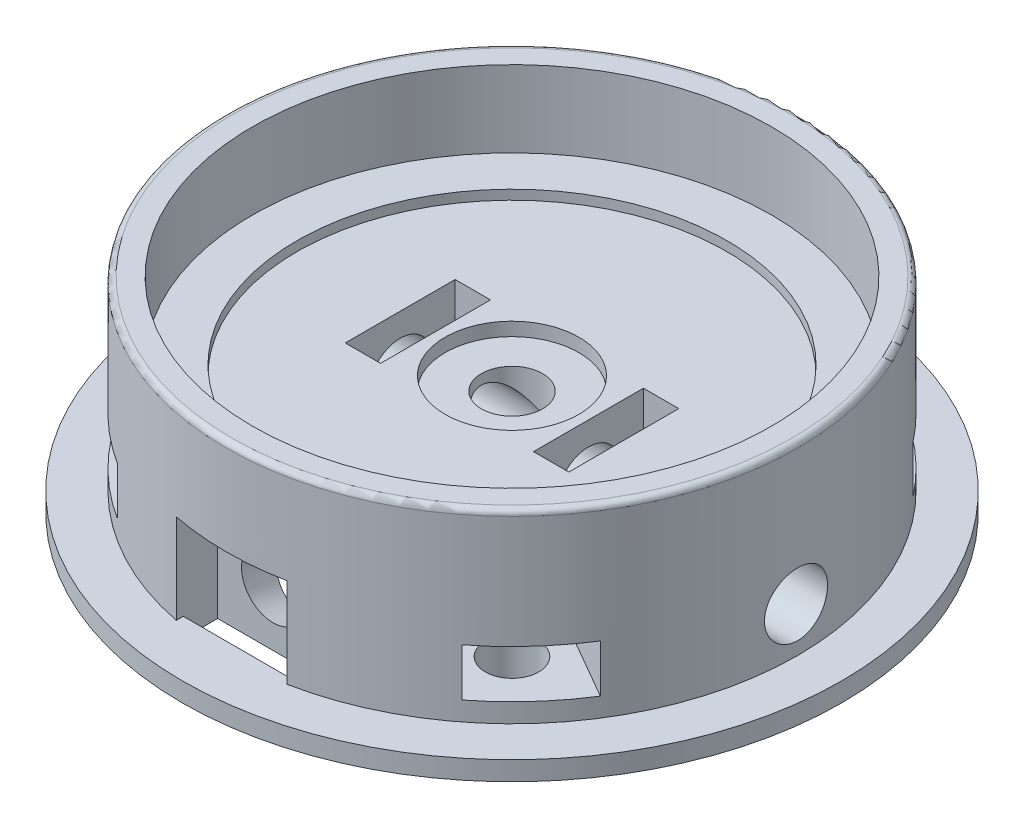
SolidWorks part; units mm, degrees
ref_plane "Front Plane" through (0, 0, 0) normal (0, 0, 1) x (1, 0, 0)
ref_plane "Top Plane" through (0, 0, 0) normal (0, 1, 0) x (1, 0, 0)
ref_plane "Right Plane" through (0, 0, 0) normal (1, 0, 0) x (0, 0, -1)
sketch "Sketch1" plane through (0, 0, 0) normal (0, 1, 0) x (1, 0, 0)
  circle A0 centre (0, 0) radius 14.95
  dimension "D1" = 29.9
extrude "Boss-Extrude1" add sketch "Sketch1" along normal blind 5.7
sketch "Sketch2" plane through (0, 5.7, 0) normal (0, 1, 0) x (1, 0, 0)
  circle A0 centre (0, 0) radius 11.25
  dimension "D1" = 22.5
extrude "Cut-Extrude1" cut sketch "Sketch2" against normal blind 0.5
sketch "Sketch3" plane through (0, 5.7, 0) normal (0, 1, 0) x (1, 0, 0)
  circle A0 centre (0, 0) radius 13.575
  circle A1 centre (0, 0) radius 14.95
  circle A2 centre (0, 0) radius 14.95 construction
  dimension "D1" = 27.15
extrude "Boss-Extrude2" add sketch "Sketch3" along normal blind 4
fillet "Fillet1" radius 0.3 1 edges at (0, 9.7, 14.95)
sketch "Sketch4" plane through (0, 5.2, 0) normal (0, 1, 0) x (1, 0, 0)
  circle A0 centre (0, 0) radius 1.6
  dimension "D1" = 3.2
extrude "Cut-Extrude2" cut sketch "Sketch4" against normal through all
ref_plane "Plane1" through (4, 0, 0) normal (1, 0, 0) x (0, 0, -1)
sketch "Sketch5" plane through (0, 0, 0) normal (1, 0, 0) x (0, 0, -1)
  line L1 (1.6, 5.2) -> (-1.6, 5.2) construction
  line L2 (-2.875, -0.55) -> (2.875, -0.55) construction
  line L3 (-2.875, -0.55) -> (-2.875, 5.2) construction
  line L4 (-2.875, 5.2) -> (2.875, 5.2) construction
  line L5 (2.875, -0.55) -> (2.875, 5.2) construction
  line L6 (-2.875, -0.55) -> (2.875, 5.2) construction
  line L7 (-2.875, 5.2) -> (2.875, -0.55) construction
  circle A0 centre (0, 2.325) radius 1.65
  dimension "D1" = 3.3
  dimension "D2" = 5.75
extrude "Cut-Extrude3" cut sketch "Sketch5" along normal through all
sketch "Sketch6" plane through (0, 0, 0) normal (0, -1, 0) x (1, 0, 0)
  circle A0 centre (0, 0) radius 1.6 construction
  circle A1 centre (0, 0) radius 1.6
  circle A2 centre (0, 0) radius 17.25
  dimension "D1" = 34.5
extrude "Boss-Extrude3" add sketch "Sketch6" along normal blind 1
sketch "Sketch7" plane through (4, 0, 0) normal (1, 0, 0) x (0, 0, -1)
  line L7 (-2.875, 5.2) -> (2.875, 5.2)
  line L8 (-2.875, 5.2) -> (-2.875, -0.55)
  line L9 (-2.875, -0.55) -> (2.875, -0.55)
  line L10 (2.875, 5.2) -> (2.875, -0.55)
  line L11 (-2.875, 5.2) -> (2.875, -0.55) construction
  line L12 (-2.875, -0.55) -> (2.875, 5.2) construction
  point P1 (0, 2.325)
  dimension "D2" = 5.75
extrude "Cut-Extrude4" cut sketch "Sketch7" along normal blind 1.85
ref_axis "Axis1" through (0, 9.4, 0) along (0, -1, 0)
pattern_circular "CirPattern1" count 2 over 360 about axis through (0, 9.4, 0) along (0, -1, 0) of "Cut-Extrude4", "Cut-Extrude3"
ref_plane "Plane2" through (0, 0, 0) normal (0, 0, 1) x (0, -1, 0)
ref_plane "Plane3" through (0, 0, 12.5) normal (0, 0, 1) x (0, -1, 0)
sketch "Sketch11" plane through (0, 0, 12.5) normal (0, 0, 1) x (0, -1, 0)
  line L0 (0, 23.2225) -> (0, -23.2225) construction
  point P4 (0, 0)
ref_plane "Plane4" through (0, 2.5421, 11.9597) normal (0, 0.2079, 0.9781) x (-1, 0, 0)
sketch "Sketch9" plane through (0, 0.4189, 12.411) normal (0, 0.2079, 0.9781) x (0, -0.9781, 0.2079)
  line L0 (-11.3652, 0) -> (-2.1706, 0) construction
  line L2 (1.4283, 2.9) -> (-4.3717, 2.9) construction
  line L3 (1.4283, 2.9) -> (1.4283, -2.9) construction
  line L4 (1.4283, -2.9) -> (-4.3717, -2.9) construction
  line L5 (-4.3717, 2.9) -> (-4.3717, -2.9) construction
  line L6 (1.4283, 2.9) -> (-4.3717, -2.9) construction
  line L7 (1.4283, -2.9) -> (-4.3717, 2.9) construction
  line L8 (0.4283, 23.2225) -> (0.4283, -23.2225) construction
  circle A0 centre (-1.4717, 0) radius 1.65
  dimension "D2" = 3.3
  dimension "D1" = 5.8
  dimension "D3" = 1
extrude "Cut-Extrude5" cut sketch "Sketch9" along normal through all and the other way blind 2
sketch "Sketch10" plane through (0, 0, 12.5) normal (0, 0, 1) x (0, -1, 0)
  line L1 (0.9781, 2.9) -> (-4.6951, 2.9) construction
  line L2 (-4.6951, 2.9) -> (-4.6951, -2.9) construction
  line L3 (0.9781, -2.9) -> (-4.6951, -2.9) construction
  line L5 (0.9781, 2.9) -> (-4.6951, 2.9)
  line L6 (-4.6951, 2.9) -> (-4.6951, -2.9)
  line L7 (0.9781, -2.9) -> (-4.6951, -2.9)
  line L8 (0.9781, 2.9) -> (2.9781, 2.9)
  line L9 (2.9781, 2.9) -> (2.9781, -2.9)
  line L10 (2.9781, -2.9) -> (0.9781, -2.9)
  dimension "D1" = 2
extrude "Cut-Extrude6" cut sketch "Sketch10" along normal blind 1.8
ref_plane "Plane5" through (0, 2.2302, 10.4924) normal (0, 0.2079, 0.9781) x (-1, 0, 0)
sketch "Sketch13" plane through (0, 2.2302, 10.4924) normal (0, 0.2079, 0.9781) x (-1, 0, 0)
  line L0 (-2.4902, -0.2075) -> (-3.8756, 3.5989)
  line L1 (-3.8756, 3.5989) -> (3.8756, 3.5989)
  line L2 (3.8756, 3.5989) -> (2.4902, -0.2075)
  line L3 (0, 0.6989) -> (0, 3.5989) construction
  line L4 (-2.9, 3.5989) -> (2.9, 3.5989) construction
  circle A0 centre (0, 0.6989) radius 1.65 construction
  circle A1 centre (0, 0.6989) radius 1.65 construction
  circle A2 centre (0, 0.6989) radius 2.65 construction
  arc A3 (2.4902, -0.2075) -> (-2.4902, -0.2075) centre (0, 0.6989) cw
  dimension "D1" = 20
  dimension "D2" = 1
ref_plane "Plane6" through (0, 0, 0) normal (-1, 0, 0) x (0, -1, 0)
ref_plane "Plane7" through (0, 0, 14.95) normal (0, 0, 1) x (1, 0, 0)
sketch "Sketch14" plane through (0, 0, 0) normal (-1, 0, 0) x (0, -1, 0)
  line L0 (-3.1606, 10.2947) -> (3.2723, 0) construction
  line L3 (0.0673, 10.9808) -> (-3.1606, 10.2947) construction
  line L5 (-3.1606, 10.2947) -> (-0.9985, 0.1229) construction
  arc A0 (-3.1606, 10.2947) -> (3.2723, 0) centre (14.1981, 13.9844) ccw
  dimension "D1" = 70
sweep "Cut-Sweep1" cut profiles "Sketch13" path "Sketch14"
sketch "Sketch19" plane through (0, 0, 14.95) normal (0, 0, 1) x (1, 0, 0)
  line L0 (2.9, 4.6951) -> (-2.9, 4.6951) construction
  line L1 (2.9, 4.6951) -> (-2.9, 4.6951)
  line L2 (14.95, 0) -> (-14.95, 0) construction
  line L3 (2.9, 0) -> (-2.9, 0)
  line L4 (-2.9, 4.6951) -> (-2.9, 0)
  line L5 (2.9, 4.6951) -> (2.9, 0)
  spline S0 degree 3 poles (-0.1103, 0.7763) (0.2206, 0.7763) (0.4399, 0.8212) (0.8405, 0.99) (1.0254, 1.1159) (1.2535, 1.3495) (1.3227, 1.4364) (1.4409, 1.6192) (1.4907, 1.7158) (1.5713, 1.9192) (1.6018, 2.0256) (1.6413, 2.2393) (1.6508, 2.3478) (1.6481, 2.6782) (1.6047, 2.8939) (1.4812, 3.1989) (1.431, 3.2954) (1.313, 3.4783) (1.2443, 3.5654) (1.0179, 3.8015) (0.8351, 3.9301) (0.4362, 4.1039) (0.2169, 4.1502) (-0.1103, 4.15) (-0.221, 4.1383) (-0.434, 4.0932) (-0.5375, 4.06) (-0.8386, 3.9282) (-1.0184, 3.8015) (-1.2465, 3.5629) (-1.3137, 3.4773) (-1.4313, 3.2948) (-1.4822, 3.1968) (-1.5641, 2.9938) (-1.5952, 2.8896) (-1.6378, 2.6758) (-1.6492, 2.5653) (-1.6515, 2.2381) (-1.6108, 2.0182) (-1.4501, 1.6141) (-1.3285, 1.4262) (-1.1006, 1.193) (-1.0155, 1.1217) (-0.835, 0.9992) (-0.7396, 0.9473) (-0.5381, 0.8627) (-0.4321, 0.8302) (-0.2188, 0.7873) (-0.1103, 0.7763) (0.2206, 0.7763) (0.4399, 0.8212) knots -0.03125 -0.03125 0 0 0.0625 0.0625 0.125 0.125 0.15625 0.15625 0.1875 0.1875 0.21875 0.21875 0.25 0.25 0.3125 0.3125 0.34375 0.34375 0.375 0.375 0.4375 0.4375 0.5 0.5 0.53125 0.53125 0.5625 0.5625 0.625 0.625 0.65625 0.65625 0.6875 0.6875 0.71875 0.71875 0.75 0.75 0.8125 0.8125 0.875 0.875 0.90625 0.90625 0.9375 0.9375 0.96875 0.96875 1 1 1.0625 1.0625 1.125 only from (0, 0.7763) to (0, 0.7763) construction
  spline S1 degree 3 poles (-0.1103, 0.7763) (0.2206, 0.7763) (0.4399, 0.8212) (0.8405, 0.99) (1.0254, 1.1159) (1.2535, 1.3495) (1.3227, 1.4364) (1.4409, 1.6192) (1.4907, 1.7158) (1.5713, 1.9192) (1.6018, 2.0256) (1.6413, 2.2393) (1.6508, 2.3478) (1.6481, 2.6782) (1.6047, 2.8939) (1.4812, 3.1989) (1.431, 3.2954) (1.313, 3.4783) (1.2443, 3.5654) (1.0179, 3.8015) (0.8351, 3.9301) (0.4362, 4.1039) (0.2169, 4.1502) (-0.1103, 4.15) (-0.221, 4.1383) (-0.434, 4.0932) (-0.5375, 4.06) (-0.8386, 3.9282) (-1.0184, 3.8015) (-1.2465, 3.5629) (-1.3137, 3.4773) (-1.4313, 3.2948) (-1.4822, 3.1968) (-1.5641, 2.9938) (-1.5952, 2.8896) (-1.6378, 2.6758) (-1.6492, 2.5653) (-1.6515, 2.2381) (-1.6108, 2.0182) (-1.4501, 1.6141) (-1.3285, 1.4262) (-1.1006, 1.193) (-1.0155, 1.1217) (-0.835, 0.9992) (-0.7396, 0.9473) (-0.5381, 0.8627) (-0.4321, 0.8302) (-0.2188, 0.7873) (-0.1103, 0.7763) (0.2206, 0.7763) (0.4399, 0.8212) knots -0.03125 -0.03125 0 0 0.0625 0.0625 0.125 0.125 0.15625 0.15625 0.1875 0.1875 0.21875 0.21875 0.25 0.25 0.3125 0.3125 0.34375 0.34375 0.375 0.375 0.4375 0.4375 0.5 0.5 0.53125 0.53125 0.5625 0.5625 0.625 0.625 0.65625 0.65625 0.6875 0.6875 0.71875 0.71875 0.75 0.75 0.8125 0.8125 0.875 0.875 0.90625 0.90625 0.9375 0.9375 0.96875 0.96875 1 1 1.0625 1.0625 1.125 only from (0, 0.7763) to (0, 0.7763) construction
extrude "Cut-Extrude11" cut sketch "Sketch19" against normal up to surface (0.65 mm away) up to face at (0, 1.8476, 14.3)
pattern_circular "CirPattern2" count 2 over 360 about axis through (0, 9.4, 0) along (0, -1, 0) of "Cut-Extrude5", "Cut-Sweep1", "Cut-Extrude6", "Cut-Extrude11"
sketch "Sketch16" plane through (0, -1, 0) normal (0, -1, 0) x (1, 0, 0)
  line L0 (0, 0) -> (-12.1976, 12.1976) construction
  line L1 (0, 11.1539) -> (0, -11.1539) construction
  circle A0 centre (0, 0) radius 17.25 construction
  circle A1 centre (-8.5206, 8.5206) radius 1.4
  circle A2 centre (-8.5206, 8.5206) radius 2.9 construction
  circle A3 centre (0, 0) radius 14.95 construction
  dimension "D2" = 2.8
  dimension "D3" = 5.8
  dimension "D1" = 45
extrude "Cut-Extrude8" cut sketch "Sketch16" against normal blind 4.5
sketch "Sketch17" plane through (0, 3.5, 0) normal (0, -1, 0) x (1, 0, 0)
  line L0 (0, 11.1539) -> (0, -11.1539) construction
  line L1 (-9.964, 11.0206) -> (-11.4074, 8.5206) construction
  line L2 (-11.4074, 8.5206) -> (-9.964, 6.0206)
  line L3 (-9.964, 6.0206) -> (-7.0773, 6.0206)
  line L4 (-7.0773, 6.0206) -> (-5.6339, 8.5206)
  line L5 (-5.6339, 8.5206) -> (-7.0773, 11.0206)
  line L6 (-7.0773, 11.0206) -> (-9.964, 11.0206) construction
  line L7 (-7.0773, 11.0206) -> (-8.0109, 12.6377)
  line L8 (-8.0109, 12.6377) -> (-12.341, 10.1377)
  line L9 (-12.341, 10.1377) -> (-11.4074, 8.5206)
  circle A0 centre (-8.5206, 8.5206) radius 2.5 construction
  circle A1 centre (0, 0) radius 14.95 construction
  dimension "D1" = 5
  dimension "D2" = 30
extrude "Cut-Extrude9" cut sketch "Sketch17" along normal blind 2.5
pattern_circular "CirPattern3" count 4 over 360 about axis through (0, 9.4, 0) along (0, -1, 0) of "Cut-Extrude8", "Cut-Extrude9"
sketch "Sketch18" plane through (0, 5.2, 0) normal (0, 1, 0) x (1, 0, 0)
  circle A2 centre (0, 0) radius 3.5
  dimension "D1" = 7
extrude "Cut-Extrude10" cut sketch "Sketch18" against normal blind 0.7
